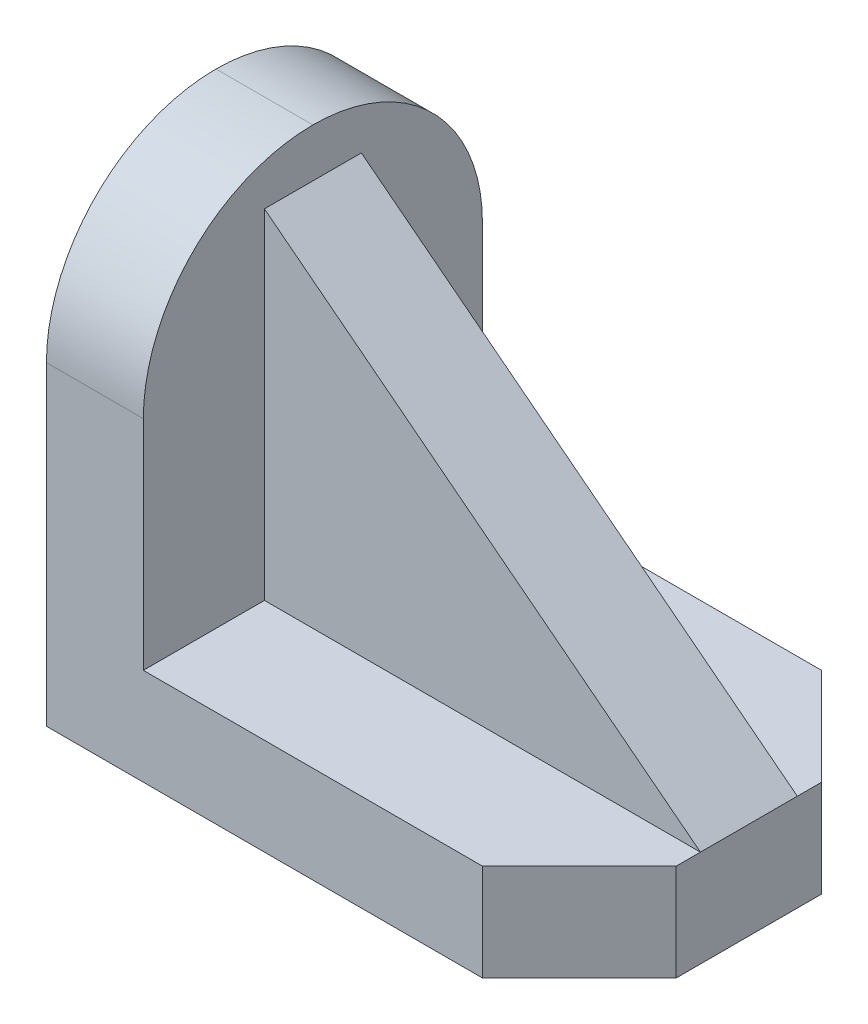
SolidWorks part; units mm, degrees
ref_plane "Front Plane" through (0, 0, 0) normal (0, 0, 1) x (1, 0, 0)
ref_plane "Top Plane" through (0, 0, 0) normal (0, 1, 0) x (1, 0, 0)
ref_plane "Right Plane" through (0, 0, 0) normal (1, 0, 0) x (0, 0, -1)
sketch "Sketch1" plane through (0, 0, 0) normal (0, 1, 0) x (1, 0, 0)
  line L1 (-33, 21) -> (33, 21)
  line L2 (-33, 21) -> (-33, -21)
  line L3 (-33, -21) -> (33, -21)
  line L4 (33, 21) -> (33, -21)
  line L5 (-33, 21) -> (33, -21) construction
  line L6 (-33, -21) -> (33, 21) construction
  point P0 (0, 0)
  dimension "D1" = 66
  dimension "D2" = 42
extrude "Boss-Extrude4" add sketch "Sketch1" along normal blind 12 contours L1 L4 L3 L2
chamfer "Chamfer2" distance 12 2 edges at (33, 6, -21) (33, 6, 21)
sketch "Sketch7" plane through (0, 12, 0) normal (0, 1, 0) x (1, 0, 0)
  line L0 (-33, -21) -> (21, -21) construction
  line L1 (-33, 21) -> (-21, 21)
  line L2 (-33, 21) -> (-33, -21)
  line L3 (-33, -21) -> (-21, -21)
  line L4 (-21, 21) -> (-21, -21)
  dimension "D1" = 12
extrude "Boss-Extrude5" add sketch "Sketch7" along normal blind 48
fillet "Fillet2" radius 21 2 edges at (-27, 60, -21) (-27, 60, 21)
sketch "Sketch8" plane through (0, 0, 0) normal (0, 0, 1) x (1, 0, 0)
  line L0 (-21, 54) -> (-21, 12)
  line L2 (-21, 12) -> (33, 12)
  line L3 (33, 12) -> (-21, 54)
  point P5 (-67.1889, 54.0476)
  point P8 (-21, 49.5)
  dimension "D1" = 42
extrude "Boss-Extrude6" add sketch "Sketch8" along normal mid plane 12
